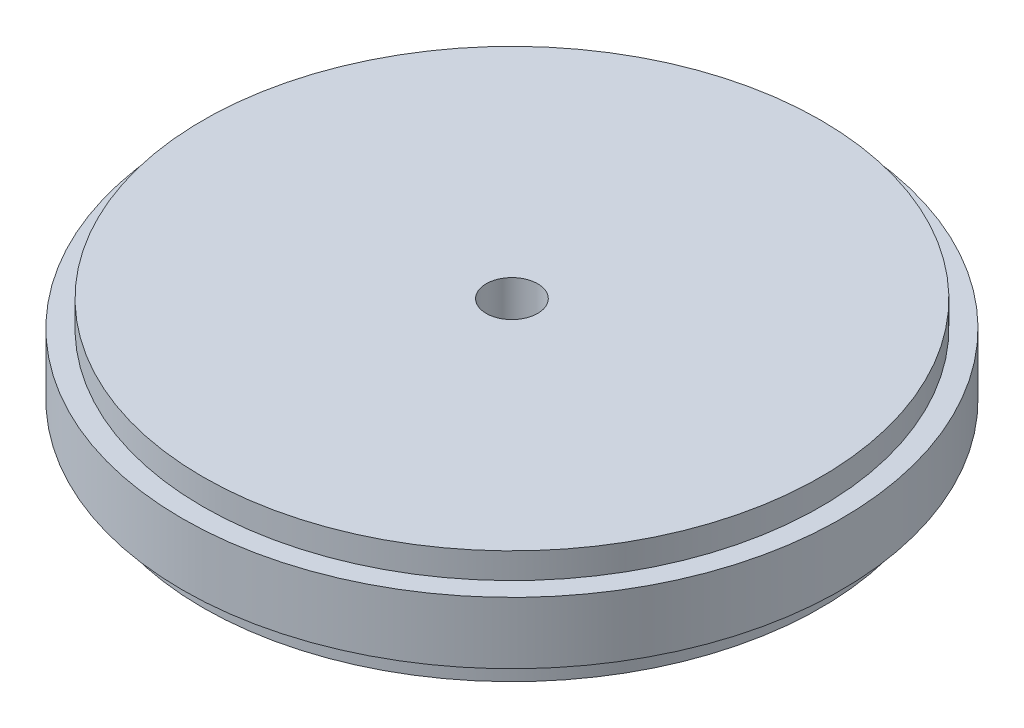
SolidWorks part; units mm, degrees
ref_plane "前视基准面" through (0, 0, 0) normal (0, 0, 1) x (1, 0, 0)
ref_plane "上视基准面" through (0, 0, 0) normal (0, 1, 0) x (1, 0, 0)
ref_plane "右视基准面" through (0, 0, 0) normal (1, 0, 0) x (0, 0, -1)
sketch "草图1" plane through (0, 0, 0) normal (0, 1, 0) x (1, 0, 0)
  circle A0 centre (0, 0) radius 32
  circle A1 centre (0, 0) radius 30
  circle A2 centre (0, 0) radius 9
  circle A3 centre (0, 0) radius 2.5
extrude "凸台-拉伸1" add sketch "草图1" along normal mid plane 6 contours A0 A1 region at (-31.0949, 0, 0)
extrude "凸台-拉伸2" add sketch "草图1<3>" along normal mid plane 11 contours A1 A2 region at (-29.1515, 0, 0)
sketch "草图1<3>" plane through (0, 0, 0) normal (0, 1, 0) x (1, 0, 0) same geometry as "草图1"
extrude "凸台-拉伸3" add sketch "草图1<5>" along normal blind 5.5 contours A2 A3 region at (-8.7454, 0, 0)
sketch "草图1<5>" plane through (0, 0, 0) normal (0, 1, 0) x (1, 0, 0) same geometry as "草图1"
extrude "凸台-拉伸4" add sketch "草图1<6>" against normal blind 14 contours A2 A3 region at (-8.7454, 0, 0)
sketch "草图1<6>" plane through (0, 0, 0) normal (0, 1, 0) x (1, 0, 0) same geometry as "草图1"
